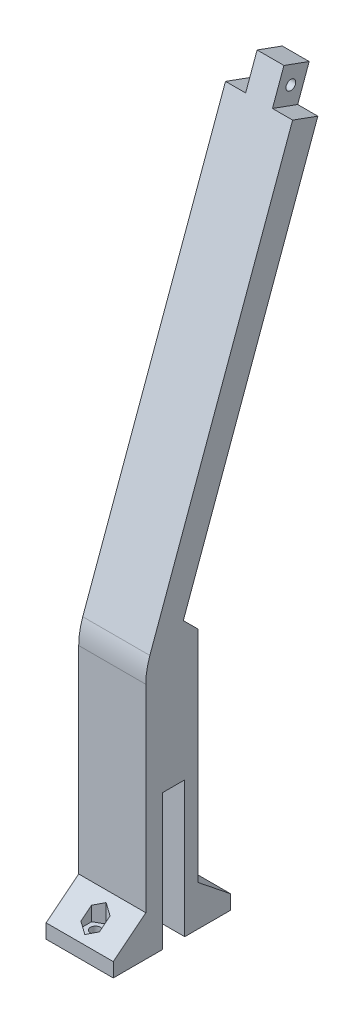
SolidWorks part; units mm, degrees
ref_plane "Front Plane" through (0, 0, 0) normal (0, 0, 1) x (1, 0, 0)
ref_plane "Top Plane" through (0, 0, 0) normal (0, 1, 0) x (1, 0, 0)
ref_plane "Right Plane" through (0, 0, 0) normal (1, 0, 0) x (0, 0, -1)
sketch "Sketch2" plane through (0, 0, 0) normal (1, 0, 0) x (0, 0, -1)
  line L0 (36.0729, 122.5) -> (-51.2799, -117.5)
  line L1 (-51.2799, -117.5) -> (-51.2799, -192)
  line L5 (-42.7665, -117.5) -> (42.7665, 117.5)
  line L6 (192.7665, 122.5) -> (36.0729, 122.5)
  line L7 (-42.7665, -117.5) -> (-35.6799, -117.5)
  line L9 (-39.6799, -151.5) -> (-46.2799, -151.5)
  line L10 (-46.2799, -151.5) -> (-46.2799, -192)
  line L13 (-35.6799, -117.5) -> (-35.6799, -192)
  line L14 (-35.6799, -192) -> (-39.6799, -192)
  line L15 (-39.6799, -192) -> (-39.6799, -151.5)
  line L16 (-51.2799, -192) -> (-46.2799, -192)
  line L18 (192.7665, 122.5) -> (192.7665, 117.5)
  line L19 (192.7665, 117.5) -> (42.7665, 117.5)
  dimension "D1" = 34
  dimension "D2" = 4
  dimension "D3" = 5
  dimension "D4" = 6.6
  dimension "D5" = 150
  dimension "D6" = 5
  dimension "D7" = 40.5
  dimension "D9" = 240
  dimension "D10" = 8
  dimension "D11" = 70
extrude "Boss-Extrude1" add sketch "Sketch2" along normal mid plane 20
chamfer "Chamfer1" distance 10 angle 45 1 edges at (0, -117.5, 42.7665) first distance on face at (0, -117.5, 39.2232)
sketch "Sketch6" plane through (10, 0, 0) normal (1, 0, 0) x (0, 0, -1)
  line L0 (-51.2799, -180) -> (-66.2799, -192)
  line L1 (-66.2799, -192) -> (-51.2799, -192)
  line L2 (-51.2799, -192) -> (-51.2799, -180)
  line L3 (-51.2799, -117.5) -> (-51.2799, -192) construction
  line L4 (-35.6799, -192) -> (-20.6799, -192)
  line L5 (-20.6799, -192) -> (-35.6799, -180)
  line L6 (-35.6799, -192) -> (-35.6799, -114.5866) construction
  line L7 (-35.6799, -180) -> (-35.6799, -192)
  dimension "D1" = 15
  dimension "D2" = 12
extrude "Boss-Extrude2" add sketch "Sketch6" against normal up to vertex (20 mm away) up to point (-10, -192, 51.2799)
sketch "Sketch7" plane through (0, -192, 0) normal (0, -1, 0) x (-1, 0, 0)
  line L0 (0, -66.2799) -> (0, -46.2799) construction
  line L1 (10, -66.2799) -> (-10, -66.2799) construction
  line L2 (-10, -46.2799) -> (10, -46.2799) construction
  line L3 (0, -20.6799) -> (0, -39.6799) construction
  line L4 (10, -20.6799) -> (-10, -20.6799) construction
  line L5 (-10, -39.6799) -> (10, -39.6799) construction
  circle A0 centre (0, -56.2799) radius 1.5
  circle A1 centre (0, -30.1799) radius 1.5
  dimension "D1" = 3
  dimension "D2" = 3
extrude "Cut-Extrude1" cut sketch "Sketch7" against normal blind 20
ref_plane "Plane1" through (0, -187, 0) normal (0, -1, 0) x (-1, 0, 0)
sketch "Sketch9" plane through (0, -187, 0) normal (0, -1, 0) x (-1, 0, 0)
  line L1 (2.75, -57.8676) -> (2.75, -54.6922)
  line L2 (2.75, -54.6922) -> (0, -53.1045)
  line L3 (0, -53.1045) -> (-2.75, -54.6922)
  line L4 (-2.75, -54.6922) -> (-2.75, -57.8676)
  line L5 (-2.75, -57.8676) -> (0, -59.4554)
  line L6 (0, -59.4554) -> (2.75, -57.8676)
  line L7 (2.75, -31.7676) -> (2.75, -28.5922)
  line L8 (2.75, -28.5922) -> (0, -27.0045)
  line L9 (0, -27.0045) -> (-2.75, -28.5922)
  line L10 (-2.75, -28.5922) -> (-2.75, -31.7676)
  line L11 (-2.75, -31.7676) -> (0, -33.3554)
  line L12 (0, -33.3554) -> (2.75, -31.7676)
  circle A0 centre (0, -56.2799) radius 2.75 construction
  circle A1 centre (0, -30.1799) radius 2.75 construction
  dimension "D1" = 5.5
  dimension "D2" = 5.5
extrude "Cut-Extrude3" cut sketch "Sketch9" against normal blind 20
fillet "Fillet5" radius 20 1 edges at (0, -117.5, 51.2799)
fillet "Fillet6" radius 10 1 edges at (0, 122.5, -36.0729)
sketch "Sketch10" plane through (10, 0, 0) normal (1, 0, 0) x (0, 0, -1)
  line L0 (-51.2799, -180) -> (-66.2799, -192) construction
  line L1 (-66.2799, -192) -> (-60.9799, -192)
  line L2 (-66.2799, -192) -> (-66.2799, -187.76)
  line L3 (-66.2799, -187.76) -> (-60.9799, -187.76)
  line L4 (-60.9799, -192) -> (-60.9799, -187.76)
  line L6 (-43.4799, -150) -> (-43.4799, -190.5) construction
  line L8 (-25.9799, -192) -> (-25.9799, -187.76)
  line L9 (-20.6799, -187.76) -> (-25.9799, -187.76)
  line L10 (-20.6799, -192) -> (-20.6799, -187.76)
  line L11 (-20.6799, -192) -> (-25.9799, -192)
  dimension "D1" = 35
extrude "Cut-Extrude4" cut sketch "Sketch10" against normal through all
sketch "Sketch11" plane through (0, 122.5, 0) normal (0, 1, 0) x (1, 0, 0)
  line L5 (-10, 43.075) -> (10, 43.075) construction
  line L6 (-10, 192.7665) -> (-6.25, 192.7665)
  line L7 (-10, 192.7665) -> (-10, 48.075)
  line L8 (-10, 48.075) -> (-6.25, 48.075)
  line L9 (-6.25, 192.7665) -> (-6.25, 48.075)
  line L10 (10, 192.7665) -> (6.25, 192.7665)
  line L11 (10, 192.7665) -> (10, 48.075)
  line L12 (10, 48.075) -> (6.25, 48.075)
  line L13 (6.25, 192.7665) -> (6.25, 48.075)
  dimension "D1" = 12.5
  dimension "D2" = 5
extrude "Cut-Extrude5" cut sketch "Sketch11" against normal through all
sketch "Sketch13" plane through (6.25, 0, 0) normal (1, 0, 0) x (0, 0, -1)
  line L0 (52.7665, 117.5) -> (37.7665, 103.7626)
  line L1 (192.7665, 117.5) -> (48.075, 117.5) construction
  line L2 (-40.098, -110.1685) -> (42.7665, 117.5) construction
  line L3 (37.7665, 103.7626) -> (42.7665, 117.5)
  line L4 (42.7665, 117.5) -> (52.7665, 117.5)
  dimension "D1" = 10
  dimension "D2" = 15
extrude "Boss-Extrude4" add sketch "Sketch13" against normal blind 12.5
sketch "Sketch12" plane through (0, 0, -192.7665) normal (0, 0, -1) x (-1, 0, 0)
  line L0 (-6.25, 117.5) -> (-6.25, 122.5) construction
  line L1 (-6.25, 120.75) -> (-4.25, 120.75)
  line L2 (-6.25, 120.75) -> (-6.25, 119.25)
  line L3 (-6.25, 119.25) -> (-4.25, 119.25)
  line L4 (-4.25, 120.75) -> (-4.25, 119.25)
  line L5 (0, 122.5) -> (0, 117.5) construction
  line L6 (-6.25, 122.5) -> (6.25, 122.5) construction
  line L7 (-6.25, 117.5) -> (6.25, 117.5) construction
  line L8 (4.25, 120.75) -> (4.25, 119.25)
  line L9 (6.25, 119.25) -> (4.25, 119.25)
  line L10 (6.25, 120.75) -> (6.25, 119.25)
  line L11 (6.25, 120.75) -> (4.25, 120.75)
  line L12 (-6.25, 122.5) -> (-6.25, 120.75) construction
  line L13 (-6.25, 117.5) -> (-6.25, 119.25) construction
  dimension "D1" = 1.75
  dimension "D2" = 1.5
  dimension "D3" = 2
extrude "Cut-Extrude6" cut sketch "Sketch12" against normal up to vertex (144.6915 mm away) up to point (10, 122.5, -48.075)
sketch "Sketch14" plane through (10, 0, 0) normal (1, 0, 0) x (0, 0, -1)
  line L0 (-7.5175, 2.7362) -> (0, 0)
  line L1 (33.6781, 115.9202) -> (-50.0738, -114.1861) construction
  line L2 (-7.5175, 2.7362) -> (28.5355, 129.4781)
  line L4 (28.5355, 129.4781) -> (208.2695, 129.4781)
  line L6 (0, 0) -> (208.2695, 117.5864)
  line L7 (208.2695, 117.5864) -> (208.2695, 129.4781)
extrude "Cut-Extrude7" cut sketch "Sketch14" against normal through all
sketch "Sketch15" plane through (0, 2.7362, 7.5175) normal (0, 0.342, 0.9397) x (1, 0, 0)
  line L0 (-10, 0) -> (10, 0) construction
  line L1 (-4, 0) -> (4, 0)
  line L2 (-4, 0) -> (-4, 10)
  line L3 (-4, 10) -> (4, 10)
  line L4 (4, 0) -> (4, 10)
  point P7 (0, 0)
  dimension "D1" = 8
  dimension "5" = 10
extrude "Boss-Extrude5" add sketch "Sketch15" against normal up to vertex (8 mm away) up to point (-10, 0, 0)
sketch "Sketch16" plane through (10, 0, 0) normal (1, 0, 0) x (0, 0, -1)
  line L0 (-3.7588, 1.3681) -> (-0.3386, 10.765) construction
  line L3 (0, 0) -> (-7.5175, 2.7362) construction
  line L4 (3.4202, 9.3969) -> (-4.0973, 12.1331) construction
  circle A0 centre (-2.0487, 6.0665) radius 1.45
  dimension "D2" = 2.9
extrude "Cut-Extrude9" cut sketch "Sketch16" against normal through all
